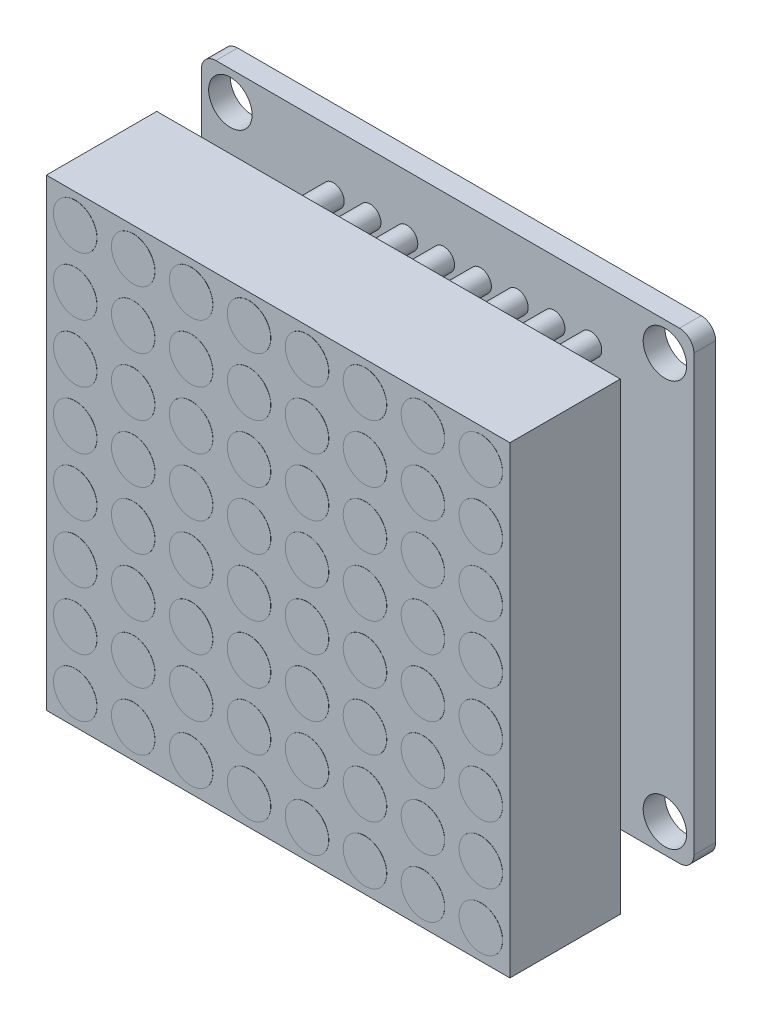
SolidWorks part; units mm, degrees
ref_plane "Alzado" through (0, 0, 0) normal (0, 0, 1) x (1, 0, 0)
ref_plane "Planta" through (0, 0, 0) normal (0, 1, 0) x (1, 0, 0)
ref_plane "Vista lateral" through (0, 0, 0) normal (1, 0, 0) x (0, 0, -1)
sketch "Croquis1" plane through (0, 0, 0) normal (0, 0, 1) x (1, 0, 0)
  line L0 (-22.5, 14) -> (7.5, 14) construction
  line L1 (-23.5, 16) -> (8.5, 16)
  line L2 (-24.5, 15) -> (-24.5, -15)
  line L3 (-23.5, -16) -> (8.5, -16)
  line L4 (9.5, 15) -> (9.5, -15)
  line L7 (-22.5, 14) -> (-22.5, -14) construction
  line L8 (-22.5, -14) -> (7.5, -14) construction
  line L9 (7.5, -14) -> (7.5, 14) construction
  arc A0 (-23.5, -16) -> (-24.5, -15) centre (-23.5, -15) cw
  arc A1 (-23.5, 16) -> (-24.5, 15) centre (-23.5, 15) ccw
  arc A2 (9.5, 15) -> (8.5, 16) centre (8.5, 15) ccw
  arc A3 (9.5, -15) -> (8.5, -16) centre (8.5, -15) cw
  circle A4 centre (-22.5, -14) radius 1.5
  circle A5 centre (-22.5, 14) radius 1.5
  circle A6 centre (7.5, 14) radius 1.5
  circle A7 centre (7.5, -14) radius 1.5
  point P0 (0, 0)
  dimension "D3" = 1
  dimension "D4" = 1
  dimension "D5" = 1
  dimension "D6" = 1
  dimension "D7" = 2
  dimension "D1" = 2
  dimension "D2" = 2
  dimension "D8" = 2
  dimension "D9" = 32
extrude "Saliente-Extruir1" add sketch "Croquis1" along normal blind 1.5
sketch "Croquis2" plane through (0, 0, 1.5) normal (0, 0, 1) x (1, 0, 0)
  line L0 (-24.5, 15) -> (-24.5, -15) construction
  line L1 (-24.4, -6.35) -> (-21.86, -6.35)
  line L2 (-24.4, -6.35) -> (-24.4, 6.35)
  line L3 (-24.4, 6.35) -> (-21.86, 6.35)
  line L4 (-21.86, -6.35) -> (-21.86, 6.35)
  line L5 (-21.86, 0) -> (-24.4, 0) construction
  line L6 (-23.5, -16) -> (8.5, -16) construction
  line L7 (-7.5, 16) -> (-7.5, -16) construction
  line L8 (8.5, 16) -> (-23.5, 16) construction
  line L9 (-24.4, -6.35) -> (-21.86, -6.35)
  line L10 (-24.4, 6.35) -> (-21.86, 6.35)
  dimension "D1" = 2.54
  dimension "D2" = 12.7
  dimension "D3" = 0.1
  dimension "D4" = 16
extrude "Saliente-Extruir2" add sketch "Croquis2" against normal blind 2.54 from surface contours L1 L4 L3 L2 region at (-23.13, 0, 1.5) starting at face at (9, 14, 0)
sketch "Croquis3" plane through (0, 0, 1.5) normal (0, 0, 1) x (1, 0, 0)
  line L0 (8.5, 16) -> (-23.5, 16) construction
  line L1 (-22.5, 16) -> (9.5, 16) construction
  line L2 (-22.5, 16) -> (-22.5, -16) construction
  line L3 (-22.5, -16) -> (9.5, -16) construction
  line L4 (9.5, 16) -> (9.5, -16) construction
  line L5 (9.5, -15) -> (9.5, 15) construction
  line L6 (-6.5, 16) -> (-6.5, -16) construction
  line L7 (-16.66, 12) -> (3.66, 12) construction
  line L12 (-16.66, 13.9501) -> (3.66, 13.9501) construction
  line L13 (-16.66, 13.9501) -> (-16.66, 10.0499) construction
  line L14 (-16.66, 10.0499) -> (3.66, 10.0499) construction
  line L15 (3.66, 13.9501) -> (3.66, 10.0499) construction
  line L16 (-22.5, 0) -> (-6.5, 0) construction
  line L17 (-6.5, 13.9501) -> (-6.5, 10.0499) construction
  circle A0 centre (-15.39, 12) radius 0.75
  circle A1 centre (-12.85, 12) radius 0.75
  circle A2 centre (-10.31, 12) radius 0.75
  circle A3 centre (-7.77, 12) radius 0.75
  circle A4 centre (-5.23, 12) radius 0.75
  circle A5 centre (-2.69, 12) radius 0.75
  circle A6 centre (-0.15, 12) radius 0.75
  circle A7 centre (2.39, 12) radius 0.75
  circle A8 centre (2.39, -12) radius 0.75
  circle A9 centre (-0.15, -12) radius 0.75
  circle A10 centre (-2.69, -12) radius 0.75
  circle A11 centre (-5.23, -12) radius 0.75
  circle A12 centre (-7.77, -12) radius 0.75
  circle A13 centre (-10.31, -12) radius 0.75
  circle A14 centre (-12.85, -12) radius 0.75
  circle A15 centre (-15.39, -12) radius 0.75
  dimension "D2" = 8
  dimension "D3" = 4
  dimension "D4" = 1.27
  dimension "D1" = 32
  dimension "D5" = 20.32
extrude "Saliente-Extruir3" add sketch "Croquis3" along normal mid plane 5.08
sketch "Croquis4" plane through (0, 0, 4.04) normal (0, 0, 1) x (1, 0, 0)
  line L0 (-16.66, 12) -> (3.66, 12) construction
  line L1 (-16.66, 13.2) -> (3.66, 13.2)
  line L2 (-16.66, 13.2) -> (-16.66, 10.8)
  line L3 (-16.66, 10.8) -> (3.66, 10.8)
  line L4 (3.66, 13.2) -> (3.66, 10.8)
  line L5 (-6.5, 13.2) -> (-6.5, 10.8) construction
  line L6 (9.5, -15) -> (9.5, 15) construction
  line L7 (8.5, 16) -> (-23.5, 16) construction
  line L8 (-6.5, 12) -> (-6.5, -12) construction
  line L9 (-6.5, 0) -> (18.66, 0) construction
  line L10 (3.66, -13.2) -> (3.66, -10.8)
  line L11 (-16.66, -10.8) -> (3.66, -10.8)
  line L12 (-16.66, -13.2) -> (-16.66, -10.8)
  line L13 (-16.66, -13.2) -> (3.66, -13.2)
  dimension "D1" = 20.32
  dimension "D2" = 2.4
  dimension "D3" = 16
  dimension "D4" = 4
  dimension "D5" = 24
extrude "Saliente-Extruir4" add sketch "Croquis4" along normal blind 2.54
sketch "Croquis5" plane through (0, 0, 6.58) normal (0, 0, 1) x (1, 0, 0)
  line L0 (-16.66, 12) -> (3.66, 12) construction
  line L1 (-16.66, 13.2) -> (-16.66, 10.8) construction
  line L2 (3.66, 10.8) -> (3.66, 13.2) construction
  line L3 (3.66, 12) -> (-6.5, 13.2) construction
  line L4 (3.66, 13.2) -> (-16.66, 13.2) construction
  line L5 (-6.5, 13.2) -> (-6.7835, 10.8) construction
  line L6 (-16.66, 10.8) -> (3.66, 10.8) construction
  line L7 (-16.66, 12) -> (-16.66, -12) construction
  line L8 (-16.66, -10.8) -> (-16.66, -13.2) construction
  line L9 (-16.66, 0) -> (17.39, 0) construction
  circle A0 centre (-15.39, 12) radius 0.5
  circle A1 centre (-12.85, 12) radius 0.5
  circle A2 centre (-10.31, 12) radius 0.5
  circle A3 centre (-7.77, 12) radius 0.5
  circle A4 centre (-5.23, 12) radius 0.5
  circle A5 centre (-2.69, 12) radius 0.5
  circle A6 centre (-0.15, 12) radius 0.5
  circle A7 centre (2.39, 12) radius 0.5
  circle A8 centre (2.39, -12) radius 0.5
  circle A9 centre (-0.15, -12) radius 0.5
  circle A10 centre (-2.69, -12) radius 0.5
  circle A11 centre (-5.23, -12) radius 0.5
  circle A12 centre (-7.77, -12) radius 0.5
  circle A13 centre (-10.31, -12) radius 0.5
  circle A14 centre (-12.85, -12) radius 0.5
  circle A15 centre (-15.39, -12) radius 0.5
  dimension "D1" = 1.27
  dimension "D2" = 8
extrude "Cortar-Extruir1" cut sketch "Croquis5" against normal blind 1.27
sketch "Croquis6" plane through (0, 0, -2.54) normal (0, 0, -1) x (-1, 0, 0)
  line L0 (22.63, 5.08) -> (23.63, 5.08) construction
  line L1 (23.63, 5.58) -> (22.63, 5.58)
  line L2 (23.63, 5.58) -> (23.63, 4.58)
  line L3 (23.63, 4.58) -> (22.63, 4.58)
  line L4 (22.63, 5.58) -> (22.63, 4.58)
  line L13 (-9.4, 0) -> (24.4, 0) construction
  line L14 (23.13, 5.58) -> (23.13, 4.58) construction
  line L15 (21.86, 6.35) -> (21.86, -6.35) construction
  line L16 (23.63, 2.04) -> (22.63, 2.04)
  line L17 (22.63, 3.04) -> (22.63, 2.04)
  line L18 (23.63, 3.04) -> (22.63, 3.04)
  line L19 (23.63, 3.04) -> (23.63, 2.04)
  line L20 (23.63, -0.5) -> (22.63, -0.5)
  line L21 (22.63, 0.5) -> (22.63, -0.5)
  line L22 (23.63, 0.5) -> (22.63, 0.5)
  line L23 (23.63, 0.5) -> (23.63, -0.5)
  line L24 (23.63, -3.04) -> (22.63, -3.04)
  line L25 (22.63, -2.04) -> (22.63, -3.04)
  line L26 (23.63, -2.04) -> (22.63, -2.04)
  line L27 (23.63, -2.04) -> (23.63, -3.04)
  line L28 (23.63, -5.58) -> (22.63, -5.58)
  line L29 (22.63, -4.58) -> (22.63, -5.58)
  line L30 (23.63, -4.58) -> (22.63, -4.58)
  line L31 (23.63, -4.58) -> (23.63, -5.58)
  line L32 (7.5, -1002.5152) -> (7.5, 48997.4848) construction
  line L35 (24.4, 6.35) -> (24.4, -6.35) construction
  point P7 (0, 0)
  dimension "D1" = 1
  dimension "D2" = 1
  dimension "D4" = 1.27
  dimension "D5" = 5
extrude "Saliente-Extruir6" add sketch "Croquis6" along normal blind 5.08 and the other way blind 5.08 from surface starting at face at (-23.13, 0, -2.54)
sketch "Croquis11" plane through (0, 0, 6.58) normal (0, 0, 1) x (1, 0, 0)
  line L0 (8.5, 16) -> (-23.5, 16) construction
  line L1 (-22.5, 16) -> (9.5, 16)
  line L2 (-22.5, 16) -> (-22.5, -16)
  line L3 (-22.5, -16) -> (9.5, -16)
  line L4 (9.5, 16) -> (9.5, -16)
  line L5 (9.5, -15) -> (9.5, 15) construction
  dimension "D1" = 32
  dimension "D2" = 32
extrude "Saliente-Extruir8" add sketch "Croquis11" along normal blind 7.62
sketch "Croquis18" plane through (0, 0, 14.2) normal (0, 0, 1) x (1, 0, 0)
  line L0 (-22.5, -16) -> (9.5, -16) construction
  line L1 (-22.5, 16) -> (-22.5, -16) construction
  circle A0 centre (-20.5, -14) radius 1.5
  circle A1 centre (-16.5, -14) radius 1.5
  circle A2 centre (-12.5, -14) radius 1.5
  circle A3 centre (-8.5, -14) radius 1.5
  circle A4 centre (-4.5, -14) radius 1.5
  circle A5 centre (-0.5, -14) radius 1.5
  circle A6 centre (3.5, -14) radius 1.5
  circle A7 centre (7.5, -14) radius 1.5
  circle A8 centre (-16.5, -10) radius 1.5
  circle A9 centre (-12.5, -10) radius 1.5
  circle A10 centre (-8.5, -10) radius 1.5
  circle A11 centre (-4.5, -10) radius 1.5
  circle A12 centre (-0.5, -10) radius 1.5
  circle A13 centre (3.5, -10) radius 1.5
  circle A14 centre (7.5, -10) radius 1.5
  circle A15 centre (-16.5, -6) radius 1.5
  circle A16 centre (-12.5, -6) radius 1.5
  circle A17 centre (-8.5, -6) radius 1.5
  circle A18 centre (-4.5, -6) radius 1.5
  circle A19 centre (-0.5, -6) radius 1.5
  circle A20 centre (3.5, -6) radius 1.5
  circle A21 centre (7.5, -6) radius 1.5
  circle A22 centre (-16.5, -2) radius 1.5
  circle A23 centre (-12.5, -2) radius 1.5
  circle A24 centre (-8.5, -2) radius 1.5
  circle A25 centre (-4.5, -2) radius 1.5
  circle A26 centre (-0.5, -2) radius 1.5
  circle A27 centre (3.5, -2) radius 1.5
  circle A28 centre (7.5, -2) radius 1.5
  circle A29 centre (-16.5, 2) radius 1.5
  circle A30 centre (-12.5, 2) radius 1.5
  circle A31 centre (-8.5, 2) radius 1.5
  circle A32 centre (-4.5, 2) radius 1.5
  circle A33 centre (-0.5, 2) radius 1.5
  circle A34 centre (3.5, 2) radius 1.5
  circle A35 centre (7.5, 2) radius 1.5
  circle A36 centre (-16.5, 6) radius 1.5
  circle A37 centre (-12.5, 6) radius 1.5
  circle A38 centre (-8.5, 6) radius 1.5
  circle A39 centre (-4.5, 6) radius 1.5
  circle A40 centre (-0.5, 6) radius 1.5
  circle A41 centre (3.5, 6) radius 1.5
  circle A42 centre (7.5, 6) radius 1.5
  circle A43 centre (-16.5, 10) radius 1.5
  circle A44 centre (-12.5, 10) radius 1.5
  circle A45 centre (-8.5, 10) radius 1.5
  circle A46 centre (-4.5, 10) radius 1.5
  circle A47 centre (-0.5, 10) radius 1.5
  circle A48 centre (3.5, 10) radius 1.5
  circle A49 centre (7.5, 10) radius 1.5
  circle A50 centre (-16.5, 14) radius 1.5
  circle A51 centre (-12.5, 14) radius 1.5
  circle A52 centre (-8.5, 14) radius 1.5
  circle A53 centre (-4.5, 14) radius 1.5
  circle A54 centre (-0.5, 14) radius 1.5
  circle A55 centre (3.5, 14) radius 1.5
  circle A56 centre (7.5, 14) radius 1.5
  circle A57 centre (-20.5, -10) radius 1.5
  circle A58 centre (-20.5, -6) radius 1.5
  circle A59 centre (-20.5, -2) radius 1.5
  circle A60 centre (-20.5, 2) radius 1.5
  circle A61 centre (-20.5, 6) radius 1.5
  circle A62 centre (-20.5, 10) radius 1.5
  circle A63 centre (-20.5, 14) radius 1.5
  dimension "D1" = 8
  dimension "D3" = 2
  dimension "D4" = 2
  dimension "D2" = 8
extrude "Saliente-Extruir9" add sketch "Croquis18" along normal blind 0.01
